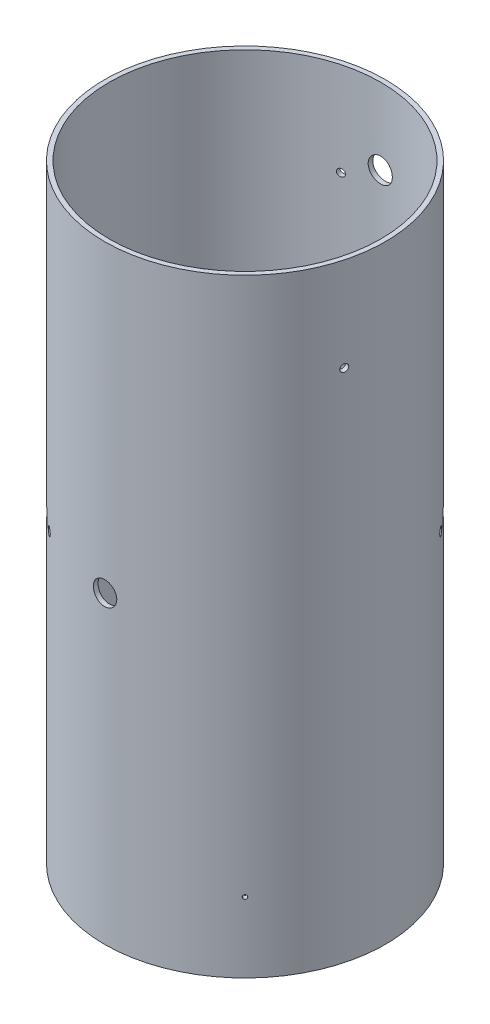
SolidWorks part; units mm, degrees
material "A-Glass Fiber"
ref_plane "Front Plane" through (0, 0, 0) normal (0, 0, 1) x (1, 0, 0)
ref_plane "Top Plane" through (0, 0, 0) normal (0, 1, 0) x (1, 0, 0)
ref_plane "Right Plane" through (0, 0, 0) normal (1, 0, 0) x (0, 0, -1)
sketch "Sketch1" plane through (0, 0, 0) normal (0, 1, 0) x (1, 0, 0)
  circle A0 centre (0, 0) radius 76.1746
  circle A1 centre (0, 0) radius 73.66
  dimension "D1" = 152.3492
  dimension "D2" = 147.32
extrude "Boss-Extrude1" add sketch "Sketch1" along normal blind 330.2
sketch "Sketch4" plane through (0, 0, 0) normal (0, 0, 1) x (1, 0, 0)
  line L0 (-76.1746, 0) -> (76.1746, 0) construction
  line L1 (76.1746, 330.2) -> (-76.1746, 330.2) construction
  line L2 (0, 330.2) -> (0, 0) construction
  line L3 (73.66, 330.2) -> (-73.66, 330.2) construction
  point P0 (0, 41.275)
  point P3 (0, 288.925)
  dimension "D1" = 41.275
  dimension "D2" = 41.275
hole_wizard "1/2 Clearance Hole5" positions "Sketch16" profile "Sketch17" hole size "1/2" standard "ANSI Inch"
sketch "Sketch16" plane through (0, 0, 0) normal (0, 0, 1) x (1, 0, 0)
  point P0 (0, 288.925)
sketch "Sketch17" plane through (0, 288.925, 0) normal (1, 0, 0) x (0, -1, 0)
  line L0 (0, 0) -> (0, 80.1345)
  line L1 (0, 80.1345) -> (6.5481, 76.2)
  line L2 (6.5481, 76.2) -> (6.5481, 0)
  line L5 (6.5481, 0) -> (0, 0)
  line L10 (0, 80.1345) -> (-6.5481, 76.2) construction
  line L11 (0, -6.35) -> (0, 107.95) construction
  dimension "Hole Dia." = 13.0962
  dimension "Hole Depth" = 76.2
  dimension "Drill Angle" = 118
sketch "Sketch27" plane through (0, 0, 0) normal (0, 0, 1) x (1, 0, 0)
  line L0 (0, 330.2) -> (0, 0) construction
  line L1 (-76.1746, 0) -> (76.1746, 0) construction
  circle A0 centre (0, 165.1) radius 6.35
  dimension "D1" = 12.7
  dimension "D2" = 165.1
extrude "Cut-Extrude1" cut sketch "Sketch27" against normal through all both and the other way through all
ref_plane "Plane1" through (0, 0, 0) normal (-0.7071, 0, 0.7071) x (0.7071, 0, 0.7071)
ref_plane "Plane2" through (0, 0, 0) normal (-0.7071, 0, 0.7071) x (0, -1, 0)
sketch "Sketch30" plane through (0, 0, 0) normal (-0.7071, 0, 0.7071) x (0.7071, 0, 0.7071)
  line L0 (0, 330.2) -> (0, 0) construction
  line L1 (4.953, 160.147) -> (-4.953, 160.147)
  line L2 (4.953, 160.147) -> (4.953, 170.053)
  line L3 (4.953, 170.053) -> (-4.953, 170.053)
  line L4 (-4.953, 160.147) -> (-4.953, 170.053)
  line L5 (4.953, 160.147) -> (-4.953, 170.053) construction
  line L6 (4.953, 170.053) -> (-4.953, 160.147) construction
  line L7 (-76.1746, 0) -> (76.1746, 0) construction
  circle A0 centre (-12.7, 165.1) radius 2.1831
  circle A1 centre (12.7, 165.1) radius 2.1831
  point P0 (0, 165.1)
  dimension "D3" = 4.3663
  dimension "D4" = 4.3663
  dimension "D1" = 9.906
  dimension "D2" = 9.906
  dimension "D5" = 12.7
  dimension "D6" = 12.7
  dimension "D7" = 165.1
extrude "Cut-Extrude2" cut sketch "Sketch30" against normal through all both and the other way through all
sketch "Sketch23" plane through (0, 0, 0) normal (-0.7071, 0, 0.7071) x (0.7071, 0, 0.7071)
  line L0 (0, 0) -> (0, 330.2) construction
  line L1 (73.66, 330.2) -> (-73.66, 330.2) construction
  line L2 (-76.1746, 165.1) -> (76.1746, 165.1) construction
  line L3 (76.1746, 0) -> (76.1746, 330.2) construction
  circle A1 centre (0, 38.1) radius 1.0922
  point P12 (0, 165.1)
  dimension "D2" = 127
extrude "Shear Scrrews" cut sketch "Sketch23" against normal through all
pattern_circular "CirPattern1" count 4 over 360 about axis through (0, 330.2, 0) along (0, -1, 0) of "Shear Scrrews"
hole_wizard "Ø4.0 (4) Diameter Hole1" positions "Sketch24" profile "Sketch25" hole size "Ø4.0" standard "ANSI Metric"
sketch "Sketch24" plane through (0, 0, 0) normal (-0.7071, 0, 0.7071) x (0, -1, 0)
  line L0 (-330.2, 76.1746) -> (-330.2, -76.1746) construction
  point P0 (-279.4, 0)
  point P5 (0, 0)
  point P6 (-279.4, 0)
  dimension "D1" = 50.8
sketch "Sketch25" plane through (0, 279.4, 0) normal (0, 1, 0) x (-0.7071, 0, -0.7071)
  line L0 (0, 0) -> (0, 90.1017)
  line L1 (0, 90.1017) -> (2, 88.9)
  line L2 (2, 88.9) -> (2, 0)
  line L5 (2, 0) -> (0, 0)
  line L10 (0, 90.1017) -> (-2, 88.9) construction
  line L11 (0, -6.35) -> (0, 107.95) construction
  dimension "Hole Dia." = 4
  dimension "Hole Depth" = 88.9
  dimension "Drill Angle" = 118
pattern_circular "CirPattern2" count 3 over 360 about axis through (0, 330.2, 0) along (0, 1, 0) of "Ø4.0 (4) Diameter Hole1"
equation "\"Mid_Coupler_Length\" = 13in"
equation "\"D1@Boss-Extrude1\"=\"Mid_Coupler_Length\""
equation "\"Shear_Screw_Coupler_Location\" = 4.5in"
equation "\"Shear_Screw_Diameter\" = 0.086in"
equation "\"D2@Sketch23\"=\"Shear_Screw_Coupler_Location\"+0.5"
equation "\"Mid_Tube_Length\"= 1in"
equation "\"Bodytube_OD\" = 6.17in"
equation "\"Bodytube_ID\" = 5.998in"
equation "\"Camera_Cutout_Width\"=10mm"
equation "\"Camera_Cutout_Height\"=7mm"
equation "\"Fwd_Tube_Length\" = 38.5in"
equation "\"BKHD_Screw_Diam\"= 3.5mm"
equation "\"Fwd_BKHD_From_Top\" = 18in"
equation "\"Motor_OD\" = 4in"
equation "\"Aft_Section_Length\"= 36in"
equation "\"AB_Coupler_OD_Length\"= 1in"
equation "\"AB_Coupling_Section_Length\"= 0.375in"
equation "\"AB_Coupler_Length\"= \"AB_Coupler_OD_Length\" + \"AB_Coupling_Section_Length\" * 2"
equation "\"Cutout_Angle\" = 80"
equation "\"AB_Paddle_Height\" = 0.375in"
equation "\"AB_Coupler_Num_Screws\"= 4"
equation "\"AB_BKHD_Thickness\" = 0.375in"
equation "\"AB_Mount_From_Bottom\" = 23.175in"
equation "\"Num_Cutouts\" = 3"
equation "\"AB_Coupler_OD\"= 6.17in"
equation "\"AB_Coupler_ID\"= 5.75in"
equation "\"AB_Coupler_Surface_Diameter\"= 5.998in"
equation "\"AB_Coupling_Screw_Diameter\"= 0.15748in"
equation "\"AB_Central_Bushing_Length\" = .4724in"
equation "\"Lead_Screw_Dist\" = 3.4in"
equation "\"Lead_Screw_Diam\" = 0.386in"
equation "\"Lead_Screw_Length\" = (\"Mid_Coupler_Length\" + 2*0.375in + 2*.75in)"
equation "\"Paddle_Pin_Offset\" = .25in"
equation "\"Paddle_Pin_Radius\" = 2.25in"
equation "\"SS_Paddle_Pin_Radius\" = 2.25*0.66in"
equation "\"Paddle_Gear_OD\" = 3.2in"
equation "\"Drive_Gear_OD\" = 1.7in"
equation "\"Fin_Thickness\"= .118in"
equation "\"Guiderail_Cutout_Diameter\"= 1.5in"
equation "\"DB9_Hole_Dist\" = 25mm"
equation "\"DB9_Relief_Width\" = 0.47in"
equation "\"DB9_Relief_Hole_Offset\" = 0.09in"
equation "\"Airbrakes_Wire_Hole_Dia\" = .25in"
equation "\"Airbrakes_Wire_Hole_Dist\" = 1.1in"
equation "\"Servo_Gear_Offset\" = 0.5in"
equation "\"FWD_Shear_Screw_Dist\" = 1.5in"
equation "\"Camera_Screw_Dia\" = 0.216535"
equation "\"Camera_Hole_Angle\" = atn ( 2 / 3 * tan ( 12.5deg ) )"
equation "\"D1@Sketch26\"=\"Camera_Cutout_Height\""
equation "\"D2@Sketch26\"=\"Camera_Cutout_Width\""
equation "\"D3@Sketch26\"=6.125"
equation "\"D1@Sketch28\"=\"Camera_Screw_Dia\""
equation "\"D2@CirPattern3\"=\"Camera_Hole_Angle\""
equation "\"D1@Sketch29\"=\"Camera_Screw_Dia\""
equation "\"D2@CirPattern4\"=\"Camera_Hole_Angle\""
equation "\"Coupler_OD\" = 5.998"
equation "\"D1@Sketch1\"=\"Coupler_OD\""
equation "\"Coupler_ID\" = 5.8"
equation "\"D2@Sketch1\"=\"Coupler_ID\""
